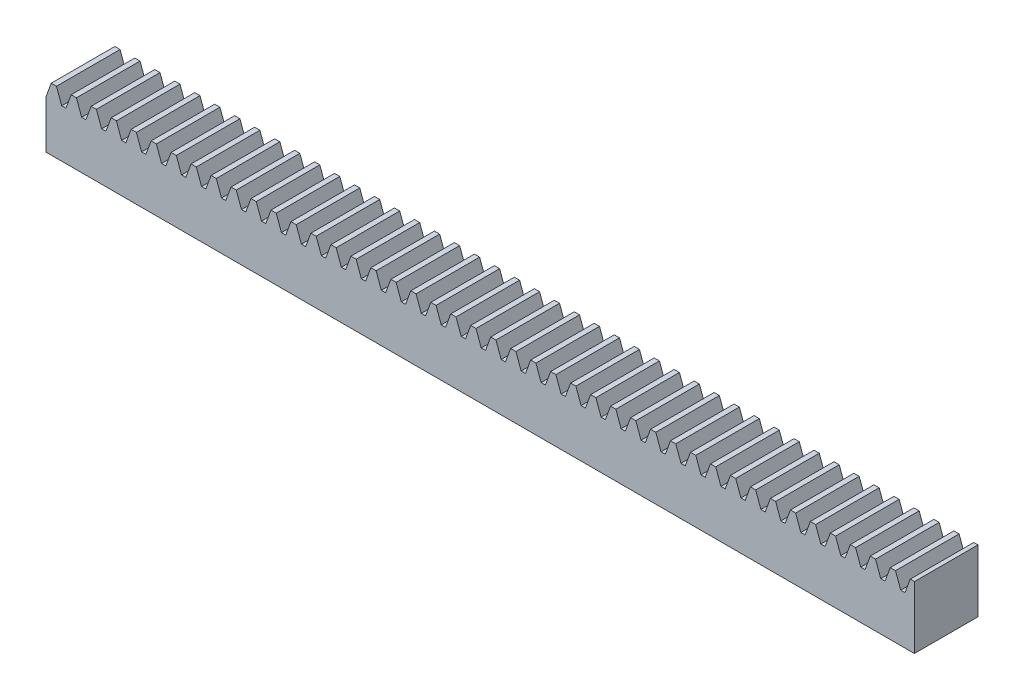
SolidWorks part; units mm, degrees
ref_plane "Front" through (0, 0, 0) normal (0, 0, 1) x (1, 0, 0)
ref_plane "Top" through (0, 0, 0) normal (0, 1, 0) x (1, 0, 0)
ref_plane "Right" through (0, 0, 0) normal (1, 0, 0) x (0, 0, -1)
sketch "Ritning 1" plane through (0, 0, 0) normal (0, 0, 1) x (1, 0, 0)
  line L1 (-124.1, -4.9) -> (125.9, -4.9)
  line L2 (-124.1, -4.9) -> (-124.1, 4.9)
  line L3 (-124.1, 4.9) -> (125.9, 4.9)
  line L4 (125.9, -4.9) -> (125.9, 4.9)
  dimension "D1" = 125.9
  dimension "D2" = 124.1
  dimension "D3" = 4.9
  dimension "D4" = 4.9
extrude "Kuggstångsämne" add sketch "Ritning 1" along normal blind 10
sketch "Ritning 2" plane through (0, 0, 10) normal (0, 0, 1) x (1, 0, 0)
  line L0 (-124.4383, 2.65) -> (-123.7617, 2.65)
  line L1 (-125.2572, 4.9) -> (-124.1, 6.0572)
  line L2 (125.9, -4.9) -> (125.9, 4.9) construction
  line L3 (-124.1, -4.9) -> (125.9, -4.9) construction
  line L7 (-124.1, 6.0572) -> (-122.9428, 4.9)
  line L9 (-122.9428, 4.9) -> (-123.7617, 2.65)
  spline S0 degree 3 poles (-125.2572, 4.9) (-124.9842, 4.15) (-124.7113, 3.4) (-124.4383, 2.65) knots 0 0 0 0 1 1 1 1
  dimension "D1" = 248.8428
  dimension "D2" = 249.6617
  dimension "D3" = 250
  dimension "D4" = 250.3383
  dimension "D5" = 7.55
  dimension "D6" = 9.8
extrude "Kugglucka" cut sketch "Ritning 2" against normal blind 10
ref_axis "Axis" through (125.9, 4.9, 10) along (-1, 0, 0)
pattern_linear "LPattern" count 80 spacing 3.1416 along (1, 0, 0) of "Kugglucka"
sketch "Sketch1" plane through (0, 0, 10) normal (0, 0, 1) x (1, 0, 0)
  line L2 (-124.1, -4.9) -> (125.9, -4.9) construction
  line L3 (-14.1, -4.9) -> (-14.1, 28.8426)
  line L4 (-14.1, 28.8426) -> (-144.1559, 20.3118)
  line L5 (-144.1559, 20.3118) -> (-144.1559, -37.129)
  line L7 (-144.1559, -37.129) -> (-16.7625, -41.11)
  line L8 (-16.7625, -41.11) -> (-14.1, -4.9)
extrude "Cut-Extrude1" cut sketch "Sketch1" against normal blind 10
sketch "Sketch2" plane through (0, 0, 10) normal (0, 0, 1) x (1, 0, 0)
  line L0 (-14.1, -4.9) -> (-12.1, -4.9)
  line L1 (-14.1, -4.9) -> (125.9, -4.9) construction
  line L2 (-12.1, -4.9) -> (-12.1, 6.4487)
  line L3 (-12.1, 6.4487) -> (-16.7862, 6.4487)
  line L4 (-16.7862, 6.4487) -> (-14.1, -4.9)
extrude "Cut-Extrude2" cut sketch "Sketch2" against normal blind 10
sketch "Sketch3" plane through (0, 0, 10) normal (0, 0, 1) x (1, 0, 0)
  line L0 (-10.6644, 2.65) -> (-10.6644, -7.0822)
  line L1 (-10.6644, -7.0822) -> (-18.0897, -7.0822)
  line L2 (-18.0897, -7.0822) -> (-18.0897, 10.598)
  line L3 (-18.0897, 10.598) -> (-10.2549, 10.598)
  line L4 (-10.2549, 10.598) -> (-10.6644, 2.65)
extrude "Cut-Extrude3" cut sketch "Sketch3" against normal blind 10
